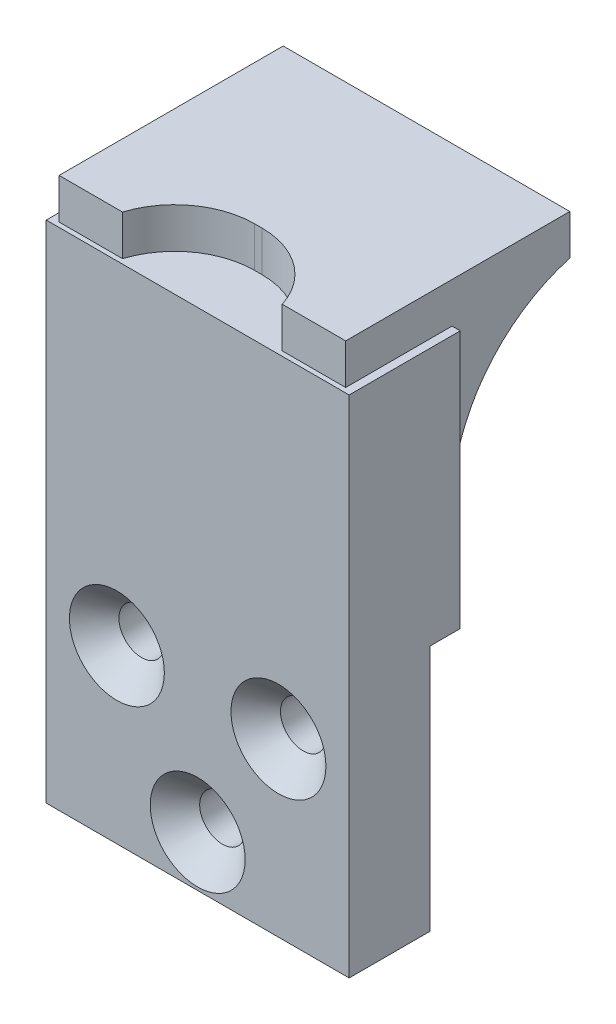
SolidWorks part; units mm, degrees
ref_plane "Front Plane" through (0, 0, 0) normal (0, 0, 1) x (1, 0, 0)
ref_plane "Top Plane" through (0, 0, 0) normal (0, 1, 0) x (1, 0, 0)
ref_plane "Right Plane" through (0, 0, 0) normal (1, 0, 0) x (0, 0, -1)
sketch "Sketch1" plane through (0, 0, 0) normal (0, 0, 1) x (1, 0, 0)
  line L0 (-15, 169.7859) -> (-15, 119.7859)
  line L1 (15, 169.7859) -> (-15, 169.7859)
  line L5 (-15, 119.7859) -> (15, 119.7859)
  line L6 (15, 119.7859) -> (15, 169.7859)
extrude "Boss-Extrude1" add sketch "Sketch1" along normal blind 10 and the other way blind 1
sketch "Sketch2" plane through (0, 169.7859, 0) normal (0, 1, 0) x (1, 0, 0)
  line L0 (14.19, 12.6594) -> (-14.19, 12.6594)
  line L1 (-14.19, 12.6594) -> (-14.19, -9.534)
  line L2 (-0.3557, -4) -> (0.3557, -4)
  line L3 (14.19, -9.534) -> (14.19, 12.6594)
  line L6 (-14.19, -9.534) -> (-7.9077, -9.534)
  line L7 (7.9077, -9.534) -> (14.19, -9.534)
  arc A1 (-0.3557, -4) -> (-7.9077, -9.534) centre (-0.3557, -11.92) ccw
  arc A2 (7.9077, -9.534) -> (0.3557, -4) centre (0.3557, -11.92) ccw
extrude "Boss-Extrude4" add sketch "Sketch2" along normal blind 4
sketch "Sketch3" plane through (0, 0, -1) normal (0, 0, -1) x (-1, 0, 0)
  line L16 (-15, 144.2481) -> (-15, 114.7859)
  line L17 (-15, 114.7859) -> (15, 114.7859)
  line L18 (15, 114.7859) -> (15, 144.2481)
  arc A2 (15, 144.2481) -> (-15, 144.2481) centre (0, -5) ccw
extrude "Cut-Extrude1" cut sketch "Sketch3" against normal blind 3
fillet "Fillet1" radius 16 1 edges at (0, 169.7859, -1)
sketch "Sketch4" plane through (0, 173.7859, 0) normal (0, 1, 0) x (1, 0, 0)
  circle A0 centre (-8.91, 3.7862) radius 1.98 construction
  circle A1 centre (8.91, 3.7862) radius 1.98 construction
  circle A2 centre (-8.91, 3.7862) radius 1.98
  circle A3 centre (8.91, 3.7862) radius 1.98
sketch "Sketch7" plane through (0, 0, 10) normal (0, 0, -1) x (-1, 0, 0)
  line L2 (0, 124.7859) -> (0, 136.7859)
  line L3 (0, 136.7859) -> (8, 136.7859)
  line L4 (0, 136.7859) -> (-8, 136.7859)
  circle A0 centre (8, 136.7859) radius 2
  circle A1 centre (0, 124.7859) radius 2
  circle A2 centre (-8, 136.7859) radius 2
hole_wizard "CSK for M4 Countersunk Flat Head Screw2" positions "Sketch11" profile "Sketch10" countersink size "M4" standard "ISO" end condition through all
sketch "Sketch11" plane through (0, 0, 10) normal (0, 0, 1) x (1, 0, 0)
  point P0 (0, 0)
  point P1 (8, 136.7859)
  point P4 (-8, 136.7859)
  point P7 (0, 124.7859)
sketch "Sketch10" plane through (0, 0, 10) normal (1, 0, 0) x (0, -1, 0)
  line L0 (0, 0) -> (0, 22.6594)
  line L1 (0, 22.6594) -> (2.25, 22.6594)
  line L2 (2.25, 22.6594) -> (2.25, 2.45)
  line L3 (2.25, 2.45) -> (4.7, 0)
  line L5 (4.7, 0) -> (0, 0)
  line L6 (-2.25, 2.45) -> (-4.7, 0) construction
  line L11 (0, -6.35) -> (0, 107.95) construction
  dimension "Thru Hole Dia." = 4.5
  dimension "Thru Hole Depth" = 22.6594
  dimension "Near C'Sink Dia." = 9.4
  dimension "Near C'Sink Angle" = 90
